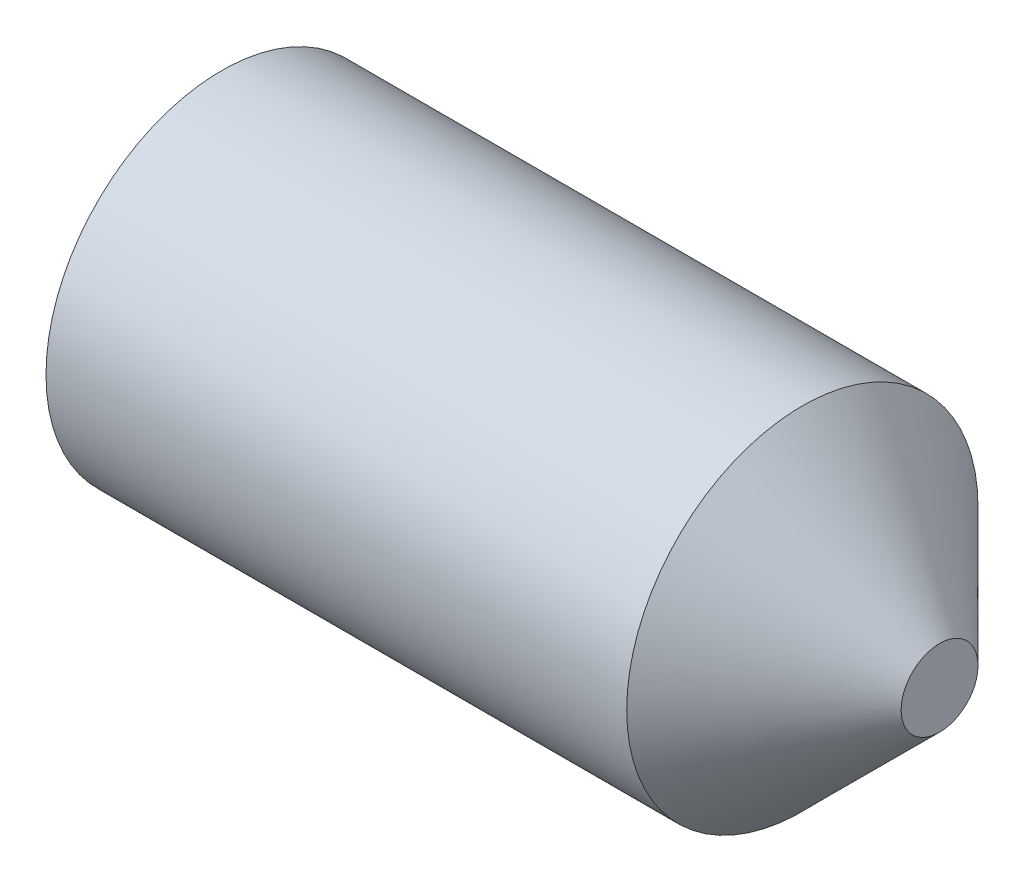
SolidWorks part; units mm, degrees
revolve "BaseBody" add sketch "BodySke" angle 360 about L5 other way angle 60
sketch "BodySke" plane through (0, 0, 0) normal (0, 0, 1) x (1, 0, 0)
  line L0 (0, 0) -> (0, 10.352)
  line L1 (0, 10.352) -> (0.9515, 12)
  line L2 (0.9515, 12) -> (40.625, 12)
  line L3 (40.625, 12) -> (50, 2.625)
  line L4 (50, 0) -> (0, 0)
  line L5 (-12.7, 0) -> (88.9, 0) construction
  line L6 (50, 2.625) -> (50, 0)
  line L7 (50, 2.625) -> (50, 12.15) construction
  line L8 (0, -10.352) -> (0.9515, -12) construction
  line L9 (3, 15.875) -> (3, -3.175) construction
  line L10 (40.625, -12) -> (50, -2.625) construction
  dimension "Length" = 50
  dimension "Cone_ang" = 90
  dimension "Diameter" = 24
cosmetic thread "ThreadCosmetic" [suppressed] parameters "Thread_minor"=20.704
ref_plane "Plane1" through (0, 0, 0) normal (0, 0, 1) x (1, 0, 0)
ref_plane "Plane2" through (0, 0, 0) normal (0, 1, 0) x (1, 0, 0)
ref_plane "Plane3" through (0, 0, 0) normal (1, 0, 0) x (0, 0, -1)
sketch "Sketch2" plane through (0, 0, 0) normal (-1, 0, 0) x (0, 0, 1)
  line L0 (3.4641, 6) -> (-3.4641, 6)
  line L1 (-3.4641, 6) -> (-6.9282, 0)
  line L2 (3.4641, 6) -> (6.9282, 0)
  line L3 (3.4641, -6) -> (6.9282, 0)
  line L4 (3.4641, -6) -> (-3.4641, -6)
  line L5 (-3.4641, -6) -> (-6.9282, 0)
  dimension "D2" = 6
  dimension "D3" = 6
extrude "Hex" cut sketch "Sketch2" against normal blind 15
sketch "ThdSchSke" [suppressed] plane through (0, 0, 0) normal (0, 0, 1) x (1, 0, 0)
  line L0 (0.9515, -10.352) -> (-0.2025, -12)
  line L1 (0.9515, -10.352) -> (2.1054, -12)
  line L2 (2.1054, -12) -> (2.1054, -15)
  line L3 (-3.175, 0) -> (5.1513, 0) construction
  line L5 (2.1054, -15) -> (-0.2025, -15)
  line L6 (-0.2025, -15) -> (-0.2025, -12)
  line L8 (0.9515, 12) -> (0.9515, -12) construction
  dimension "Thread_minor" = 20.704
  dimension "Diameter" = 24
revolve "ThreadSchematic" [suppressed] cut sketch "ThdSchSke" angle 360 about L3
pattern_linear "ThdSchPat" [suppressed]
equation "\"D2@Sketch2\" = \"Hex_size@Sketch2\" / 2"
equation "\"D3@Sketch2\" = \"Hex_size@Sketch2\" / 2"
equation "\"Thread_minor@ThreadCosmetic\" = \"Minor_dia@BodySke\""
equation "\"Thread_minor@ThdSchSke\" = \"Thread_minor@ThreadCosmetic\""
equation "\"Diameter@ThdSchSke\" = \"Diameter@BodySke\""
equation "\"Overcut@ThdSchSke\" = \"Diameter@BodySke\" * 1.25"
equation "\"Num_threads@ThdSchPat\" = int( (\"Length@BodySke\" - ( ( ( \"Diameter@BodySke\" - \"Minor_dia@BodySke\" ) * 0.5 ) / tan( \"Drive_ch_ang@BodySke\" * 0.017453292 ) ) - ( ( ( \"Diameter@BodySke\" - \"Tip_dia@BodySke\" ) * 0.5 ) / tan( \"Cone_ang@BodySke\" / 2.0 * 0.017453292 ) ) ) / \"Advance@BodySke\" + 0.999 )  + 1"
equation "\"Advance@ThdSchPat\" = (\"Length@BodySke\" - ( ( ( \"Diameter@BodySke\" - \"Minor_dia@BodySke\" ) * 0.5 ) / tan( \"Drive_ch_ang@BodySke\" * 0.017453292 ) ) - ( ( ( \"Diameter@BodySke\" - \"Tip_dia@BodySke\" ) * 0.5 ) / tan( \"Cone_ang@BodySke\" / 2.0 * 0.017453292 ) ) ) /  (\"Num_threads@ThdSchPat\" - 1) 'relax it"
equation "' \"Num_threads@ThdSchPat\" = \"Num_threads@ThdSchPat\" - sgn( \"Num_threads@ThdSchPat\" - 1) '---chamfered tips only---"
